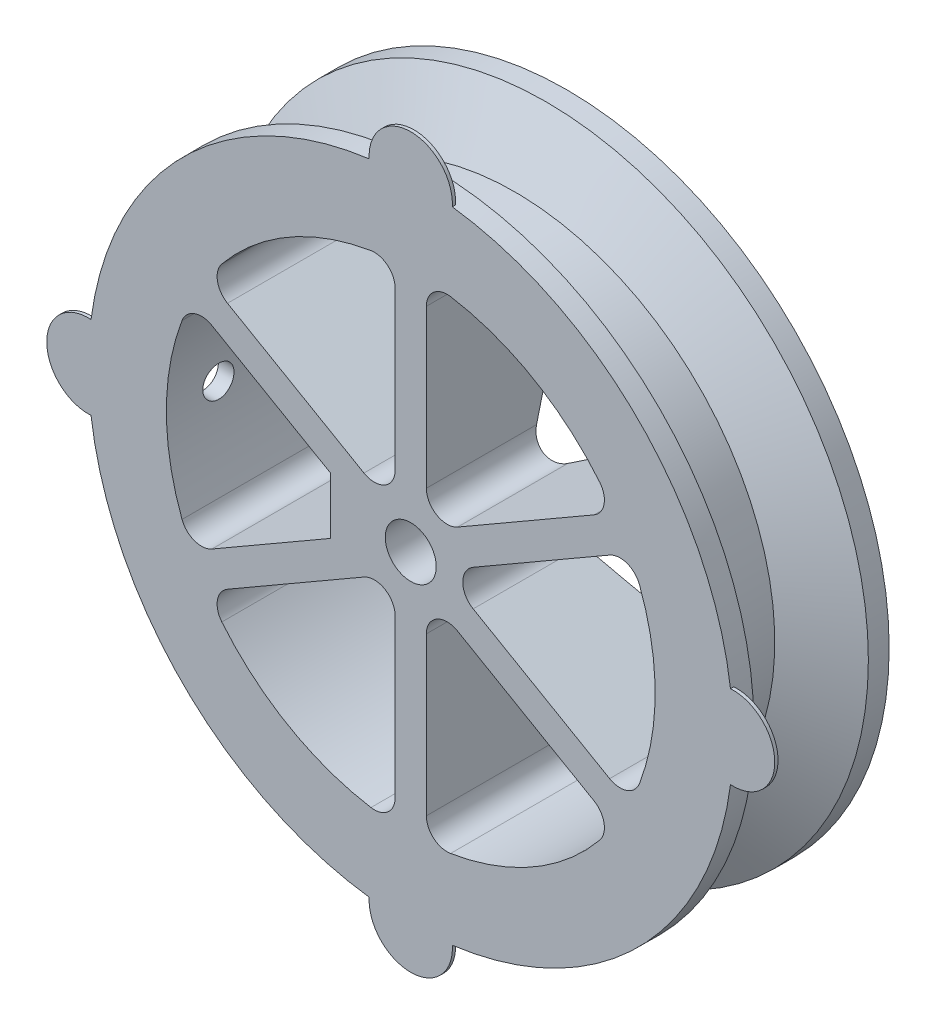
SolidWorks part; units mm, degrees
ref_plane "Front Plane" through (0, 0, 0) normal (0, 0, 1) x (1, 0, 0)
ref_plane "Top Plane" through (0, 0, 0) normal (0, 1, 0) x (1, 0, 0)
ref_plane "Right Plane" through (0, 0, 0) normal (1, 0, 0) x (0, 0, -1)
sketch "Sketch2" plane through (0, 0, 0) normal (0, 1, 0) x (1, 0, 0)
  line L0 (0, 9.525) -> (0, -9.525) construction
  line L1 (0, 9.525) -> (39.37, 9.525)
  line L2 (39.37, 9.525) -> (39.37, 6.985)
  line L3 (39.37, 6.985) -> (31.75, 3.175)
  line L4 (31.75, 3.175) -> (31.75, -6.985)
  line L5 (31.75, -6.985) -> (39.37, -6.985)
  line L6 (39.37, -6.985) -> (39.37, -9.525)
  line L7 (39.37, -9.525) -> (0, -9.525)
  line L8 (0, -9.525) -> (0, 9.525)
  line L9 (0, 0) -> (31.75, 0) construction
  dimension "D1" = 19.05
  dimension "D2" = 2.54
  dimension "D3" = 2.54
  dimension "D4" = 7.62
  dimension "D5" = 31.75
  dimension "D9" = 3.81
revolve "Revolve1" add sketch "Sketch2" angle 360 about L0
sketch "Sketch4" plane through (0, 0, 9.525) normal (0, 0, 1) x (1, 0, 0)
  circle A0 centre (0, 0) radius 3.1115
  dimension "D1" = 6.223
extrude "Cut-Extrude1" cut sketch "Sketch4" against normal through all
sketch "Sketch5" plane through (0, 0, 9.525) normal (0, 0, 1) x (1, 0, 0)
  line L0 (0, 3.175) -> (0, 31.75) construction
  line L1 (2.7496, 1.5875) -> (27.4963, 15.875) construction
  line L2 (5.715, 5.4993) -> (22.3789, 15.1202)
  line L3 (1.905, 7.699) -> (1.905, 26.9408)
  line L4 (3.1259, 4.0044) -> (24.8413, 16.5418) construction
  line L5 (1.905, 4.7093) -> (1.905, 29.7841) construction
  arc A1 (0, 31.75) -> (27.4963, 15.875) centre (0, 0) cw construction
  arc A2 (2.7496, 1.5875) -> (0, 3.175) centre (0, 0) ccw construction
  arc A3 (4.8585, 29.4469) -> (23.0725, 18.931) centre (0, 0) cw
  arc A4 (3.1259, 4.0044) -> (1.905, 4.7093) centre (0, 0) ccw
  arc A5 (5.715, 5.4993) -> (1.905, 7.699) centre (4.445, 7.699) cw
  arc A6 (1.905, 29.7841) -> (24.8413, 16.5418) centre (0, 0) cw construction
  arc A7 (4.8585, 29.4469) -> (1.905, 26.9408) centre (4.445, 26.9408) ccw
  arc A8 (23.0725, 18.931) -> (22.3789, 15.1202) centre (21.1089, 17.3199) cw
  dimension "D1" = 31.75
  dimension "D3" = 6.35
  dimension "D5" = 2.54
  dimension "D2" = 60
  dimension "D4" = 1.905
extrude "Cut-Extrude2" cut sketch "Sketch5" against normal through all contours A8 A3 A7 L3 A5 L2 | A5 L2 L3 region at (10.2965, 17.834, 9.525)
pattern_circular "CirPattern1" count 6 over 360 about axis through (0, 0, 9.525) along (0, 0, -1) of "Cut-Extrude2"
sketch "Sketch6" plane through (0, 0, 9.525) normal (0, 0, 1) x (1, 0, 0)
  line L0 (-3.1115, 0) -> (-6.35, 0) construction
  line L2 (-4.7307, -3.4645) -> (-9.8107, -3.4645)
  line L3 (-4.7307, -3.4645) -> (-4.7307, 3.4645)
  line L4 (-4.7307, 3.4645) -> (-9.8107, 3.4645)
  line L5 (-9.8107, -3.4645) -> (-9.8107, 3.4645)
  line L6 (-7.62, 2.1997) -> (-24.2839, 11.8206) construction
  circle A0 centre (0, 0) radius 3.1115 construction
  arc A1 (-7.62, -2.1997) -> (-7.62, 2.1997) centre (-8.89, 0) ccw construction
  point P11 (-4.7307, 0)
  dimension "D1" = 5.08
extrude "Boss-Extrude2" add sketch "Sketch6" against normal through all
hole_wizard "#4 Clearance Hole1" positions "Sketch8" profile "Sketch9" hole size "#4" standard "ANSI Inch"
sketch "Sketch8" plane through (-9.8107, 0, 0) normal (-1, 0, 0) x (0, 0, 1)
  line L0 (-3.175, 0) -> (6.985, 0) construction
  line L1 (-3.175, 31.75) -> (-3.175, -31.75) construction
  line L2 (6.985, 31.75) -> (6.985, -31.75) construction
  point P0 (3.175, 0)
  dimension "D1" = 3.81
sketch "Sketch9" plane through (-9.8107, 0, 3.175) normal (0, 1, 0) x (0, 0, 1)
  line L0 (0, 0) -> (0, 13.7378)
  line L1 (0, 13.7378) -> (1.7272, 12.7)
  line L2 (1.7272, 12.7) -> (1.7272, 0)
  line L5 (1.7272, 0) -> (0, 0)
  line L10 (0, 13.7378) -> (-1.7272, 12.7) construction
  line L11 (0, -6.35) -> (0, 107.95) construction
  dimension "Hole Dia." = 3.4544
  dimension "Hole Depth" = 12.7
  dimension "Drill Angle" = 118
sketch "Sketch10" plane through (-9.8107, 0, 0) normal (-1, 0, 0) x (0, 0, 1)
  circle A0 centre (3.175, 0) radius 1.905
  dimension "D1" = 3.81
extrude "Cut-Extrude3" cut sketch "Sketch10" along normal through all
sketch "Sketch15" plane through (-9.8107, 0, 0) normal (-1, 0, 0) x (0, 0, 1)
  line L0 (3.175, 0) -> (-9.525, 0) construction
  line L1 (-9.525, 39.37) -> (-9.525, -39.37) construction
  line L2 (-9.525, -3.429) -> (5.1547, -3.429)
  line L3 (-0.4912, 0) -> (1.3419, -3.175) construction
  line L4 (1.3419, -3.175) -> (5.0081, -3.175) construction
  line L5 (5.0081, -3.175) -> (6.8412, 0) construction
  line L6 (6.8412, 0) -> (5.0081, 3.175) construction
  line L7 (5.0081, 3.175) -> (1.3419, 3.175) construction
  line L8 (1.3419, 3.175) -> (-0.4912, 0) construction
  line L9 (5.1547, -3.429) -> (7.1345, 0)
  line L10 (7.1345, 0) -> (5.1547, 3.429)
  line L11 (5.1547, 3.429) -> (-9.525, 3.429)
  line L12 (5.1547, 3.429) -> (1.3419, 3.429) construction
  line L13 (1.3419, -3.429) -> (5.1547, -3.429) construction
  line L14 (-9.525, 3.429) -> (-9.525, -3.429)
  circle A0 centre (3.175, 0) radius 3.175 construction
  dimension "D1" = 6.35
  dimension "D2" = 0.254
extrude "Cut-Extrude7" cut sketch "Sketch15" against normal blind 2.413 from offset 1.778 offset against normal yes
sketch "Sketch13" plane through (0, 0, 0) normal (1, 0, 0) x (0, 0, -1)
  circle A0 centre (0, 0) radius 1
  dimension "D1" = 2
extrude "Cut-Extrude6" [suppressed] cut sketch "Sketch13" along normal through all from offset 25.4
sketch "Sketch16" plane through (0, 0, 0) normal (0, 1, 0) x (1, 0, 0)
  line L0 (0, -9.525) -> (0, 9.525) construction
  line L1 (3.1115, 9.525) -> (-3.1115, 9.525) construction
  line L2 (-39.37, -9.525) -> (39.37, -9.525) construction
  line L3 (0, 1.905) -> (29.845, 9.525)
  line L4 (29.845, 9.525) -> (0, 9.525)
  line L5 (0, 9.525) -> (0, 1.905)
  dimension "D1" = 7.62
revolve "Cut-Revolve1" cut sketch "Sketch16" angle 360 about L0
sketch "Sketch14" plane through (0, 0, 9.525) normal (0, 0, -1) x (-1, 0, 0)
  line L0 (0, 0) -> (39.37, 0) construction
  circle A0 centre (39.37, 0) radius 5.08
  circle A1 centre (0, 0) radius 39.37 construction
  circle A2 centre (0, -39.37) radius 5.08
  circle A3 centre (-39.37, 0) radius 5.08
  circle A4 centre (0, 39.37) radius 5.08
  point P15 (0, 0)
  dimension "D1" = 10.16
  dimension "D2" = 4
extrude "Print Tabs" add sketch "Sketch14" along normal blind 0.4
equation "\"spool_radius\"=1.25"
